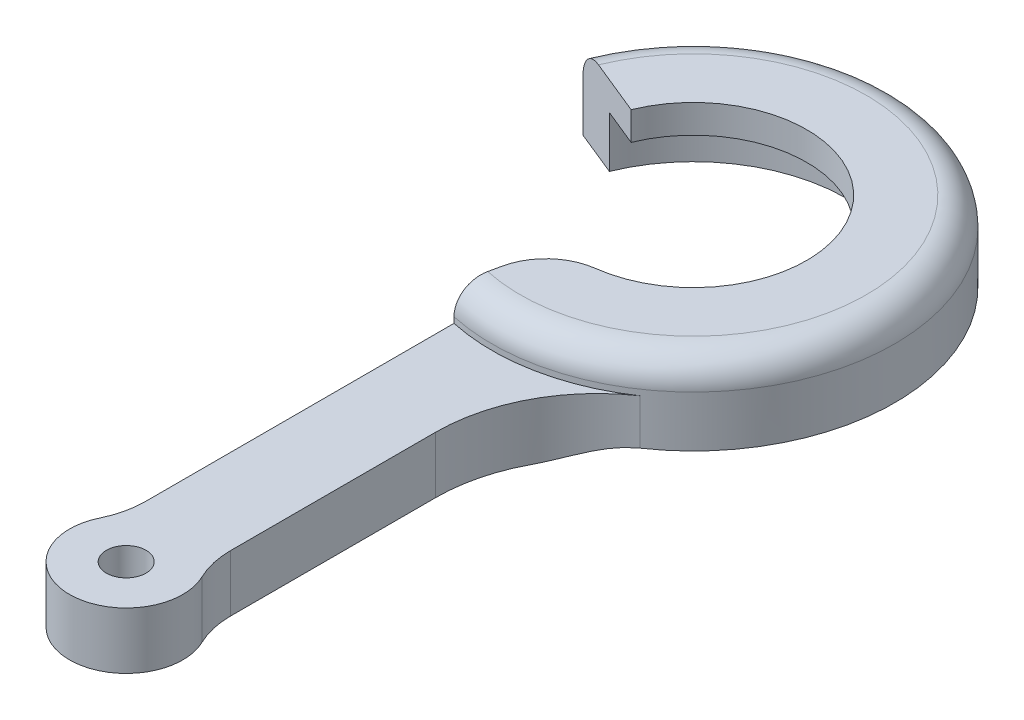
SolidWorks part; units mm, degrees
ref_plane "Front Plane" through (0, 0, 0) normal (0, 0, 1) x (1, 0, 0)
ref_plane "Top Plane" through (0, 0, 0) normal (0, 1, 0) x (1, 0, 0)
ref_plane "Right Plane" through (0, 0, 0) normal (1, 0, 0) x (0, 0, -1)
sketch "Sketch1" plane through (0, 0, 0) normal (0, 1, 0) x (1, 0, 0)
  circle A0 centre (0, 0) radius 6.858
  circle A1 centre (0, 0) radius 9.017
  dimension "D1" = 13.716
  dimension "D2" = 2.159
extrude "Boss-Extrude1" add sketch "Sketch1" along normal blind 2.286
sketch "Sketch2" plane through (0, 2.286, 0) normal (0, 1, 0) x (1, 0, 0)
  circle A0 centre (0, 0) radius 5.08
  circle M1 centre (0, 0) radius 9.017
  circle M2 centre (0, 0) radius 6.858
  dimension "D1" = 10.16
extrude "Boss-Extrude2" add sketch "Sketch2" along normal blind 1.27 contours A0 M2 | M1 M2 region at (-8.762, 2.286, 0) region at (-6.664, 2.286, 0)
sketch "Sketch3" plane through (0, 3.556, 0) normal (0, 1, 0) x (1, 0, 0)
  line L1 (1.905, 0) -> (-1.905, 0)
  line L2 (1.905, 0) -> (1.905, -25.4)
  line L3 (1.905, -25.4) -> (-1.905, -25.4)
  line L4 (-1.905, 0) -> (-1.905, -25.4)
  circle M5 centre (0, 0) radius 9.017
  dimension "D1" = 3.81
  dimension "D2" = 25.4
extrude "Boss-Extrude3" add sketch "Sketch3" against normal offset from surface (4.064 mm away) 2.794 contours L4 L3 L2 M5 region at (0, 3.556, 17.1746) up to face at (0, 2.286, 5.08) offset beyond the face yes
sketch "Sketch4" plane through (0, 3.556, 0) normal (0, 1, 0) x (1, 0, 0)
  line L3 (-1.905, -8.8135) -> (-1.905, -25.4)
  line L4 (-1.905, -25.4) -> (1.905, -25.4)
  line L5 (1.905, -25.4) -> (1.905, -8.8135)
  line L6 (-1.905, -8.8135) -> (-1.905, -25.4)
  line L7 (-1.905, -25.4) -> (1.905, -25.4)
  line L8 (1.905, -25.4) -> (1.905, -8.8135)
  circle A0 centre (0, 0) radius 9.017
  arc A1 (1.905, -8.8135) -> (-1.905, -8.8135) centre (0, 0) ccw
  arc A2 (1.905, -8.8135) -> (-1.905, -8.8135) centre (0, 0) ccw
  line M7 (-1.905, -8.8135) -> (-1.905, -25.4)
  line M8 (-1.905, -25.4) -> (1.905, -25.4)
  line M9 (1.905, -25.4) -> (1.905, -8.8135)
  dimension "D1" = 0
extrude "Cut-Extrude1" cut sketch "Sketch4" against normal offset from surface (1.524 mm away) 2.54 contours A0 M7 M8 M9 region at (0, 3.556, 17.1746) up to face at (0, -0.508, 17.1576)
sketch "Sketch5" plane through (0, 3.556, 0) normal (0, 1, 0) x (1, 0, 0)
  line L0 (-1.905, -8.8135) -> (0, 0)
  line L1 (0, 0) -> (-8.3488, 3.4065)
  line L3 (1.905, -25.4) -> (1.905, -8.8135)
  line L4 (-1.905, -8.8135) -> (-1.905, -25.4)
  line L5 (-1.905, -25.4) -> (1.905, -25.4)
  line L6 (1.905, -25.4) -> (1.905, -8.8135)
  line L7 (-1.905, -8.8135) -> (-1.905, -25.4)
  line L8 (-1.905, -25.4) -> (1.905, -25.4)
  circle A1 centre (0, 0) radius 9.017
  circle A2 centre (0, 0) radius 9.017
  arc A3 (-1.905, -8.8135) -> (1.905, -8.8135) centre (0, 0) ccw
  arc A4 (-1.905, -8.8135) -> (1.905, -8.8135) centre (0, 0) ccw
  circle M8 centre (0, 0) radius 5.08
  circle M9 centre (0, 0) radius 9.017
  dimension "D3" = 100
  dimension "D1" = 0
  dimension "D2" = 0
extrude "Cut-Extrude2" cut sketch "Sketch5" against normal through all contours L1 L0 M8 M9 | L0 L1 M8 region at (-5.6153, 3.556, 2.961) region at (-2.6297, 3.556, 1.3867)
fillet "Fillet1" radius 2.159 1 edges at (-1.4489, 1.143, 6.7032)
fillet "Fillet2" radius 2.159 1 edges at (0, -0.508, 9.017)
fillet "Fillet3" radius 7.239 1 edges at (1.905, 1.016, 8.8135)
fillet "Fillet4" radius 2.5654 1 edges at (-1.0732, 2.921, 4.9653)
fillet "Fillet5" radius 1.27 1 edges at (7.976, 3.556, -4.2059)
sketch "Sketch6" plane through (0, 2.032, 0) normal (0, 1, 0) x (1, 0, 0)
  line L3 (1.905, -25.4) -> (1.905, -13.4404)
  line L4 (-1.905, -8.8135) -> (-1.905, -25.4)
  line L5 (-1.905, -25.4) -> (1.905, -25.4)
  line L6 (1.905, -25.4) -> (1.905, -13.4404)
  line L7 (-1.905, -8.8135) -> (-1.905, -25.4)
  line L8 (-1.905, -25.4) -> (1.905, -25.4)
  circle A0 centre (0, -25.4) radius 2.54
  arc A2 (5.0721, -7.4552) -> (1.905, -13.4404) centre (9.144, -13.4404) ccw
  arc A3 (-1.905, -8.8135) -> (5.0721, -7.4552) centre (0, 0) ccw
  arc A4 (5.0721, -7.4552) -> (1.905, -13.4404) centre (9.144, -13.4404) ccw
  arc A5 (-1.905, -8.8135) -> (5.0721, -7.4552) centre (0, 0) ccw
  point P8 (0, 0)
  point P10 (0, -25.4)
  line M6 (1.905, -25.4) -> (1.905, -13.4404)
  line M10 (-1.905, -25.4) -> (1.905, -25.4)
  dimension "D2" = 5.08
  dimension "D1" = 0
extrude "Boss-Extrude4" add sketch "Sketch6" against normal up to surface (2.54 mm away) contours L7 A0 M6 M10 region at (0, 2.032, 26.2611) up to face at (0.5114, -0.508, 16.9444)
sketch "Sketch7" plane through (0, 2.032, 0) normal (0, 1, 0) x (1, 0, 0)
  line L2 (-1.905, -8.8135) -> (-1.905, -23.7199)
  line L3 (1.905, -23.7199) -> (1.905, -13.4404)
  line L4 (-1.905, -8.8135) -> (-1.905, -23.7199)
  line L5 (1.905, -23.7199) -> (1.905, -13.4404)
  circle A0 centre (0, -25.4) radius 0.889
  arc A3 (-1.905, -23.7199) -> (1.905, -23.7199) centre (0, -25.4) ccw
  arc A4 (5.0721, -7.4552) -> (1.905, -13.4404) centre (9.144, -13.4404) ccw
  arc A5 (-1.905, -8.8135) -> (5.0721, -7.4552) centre (0, 0) ccw
  arc A6 (-1.905, -23.7199) -> (1.905, -23.7199) centre (0, -25.4) ccw
  arc A7 (5.0721, -7.4552) -> (1.905, -13.4404) centre (9.144, -13.4404) ccw
  arc A8 (-1.905, -8.8135) -> (5.0721, -7.4552) centre (0, 0) ccw
  dimension "D2" = 1.778
  dimension "D1" = 0
extrude "Cut-Extrude3" cut sketch "Sketch7" against normal blind 2.54 contours A0 region at (0, 2.032, 25.4)
fillet "Fillet6" radius 3.81 2 edges at (1.905, 0.762, 23.7199) (-1.905, 0.762, 23.7199)
